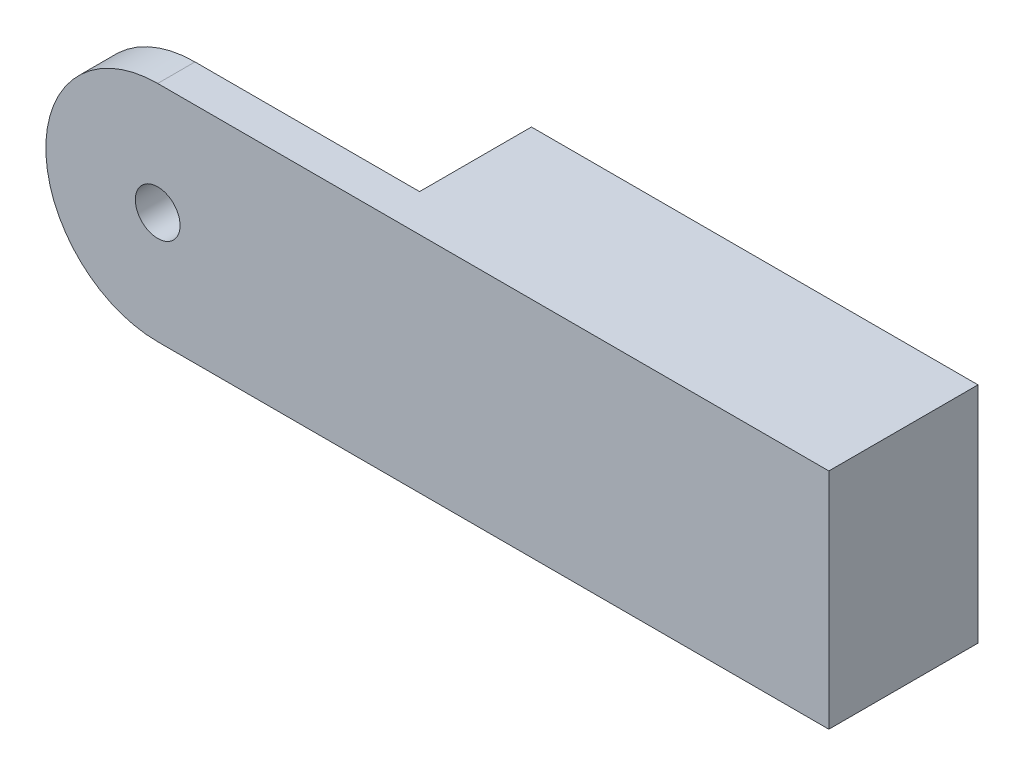
SolidWorks part; units mm, degrees
ref_plane "前视基准面" through (0, 0, 0) normal (0, 0, 1) x (1, 0, 0)
ref_plane "上视基准面" through (0, 0, 0) normal (0, 1, 0) x (1, 0, 0)
ref_plane "右视基准面" through (0, 0, 0) normal (1, 0, 0) x (0, 0, -1)
sketch "草图1" plane through (0, 0, 0) normal (0, 0, 1) x (1, 0, 0)
  line L1 (-45, 15) -> (45, 15)
  line L3 (-45, -15) -> (45, -15)
  line L4 (45, 15) -> (45, -15)
  arc A0 (-45, 15) -> (-45, -15) centre (-45, 0) ccw
  circle A1 centre (-45, 0) radius 3
  point P0 (0, 0)
  dimension "D1" = 30
extrude "凸台-拉伸1" add sketch "草图1" along normal blind 20
ref_plane "基准面1" through (0, 0, 15) normal (0, 0, 1) x (1, 0, 0)
sketch "草图2" plane through (0, 0, 15) normal (0, 0, 1) x (1, 0, 0)
  line L0 (45, 15) -> (-45, 15) construction
  line L1 (-29.6441, 15) -> (-61.6301, 15)
  line L2 (-29.6441, 15) -> (-29.6441, -15)
  line L3 (-29.6441, -15) -> (-61.6301, -15)
  line L4 (-61.6301, 15) -> (-61.6301, -15)
extrude "切除-拉伸2" cut sketch "草图2" against normal through all
sketch "草图3" plane through (0, 0, 15) normal (0, 0, 1) x (1, 0, 0)
  line L0 (45, 15) -> (-29.6441, 15) construction
  line L1 (-14.884, 15) -> (-59.884, 15)
  line L2 (-14.884, 15) -> (-14.884, -15)
  line L3 (-14.884, -15) -> (-59.884, -15)
  line L4 (-59.884, 15) -> (-59.884, -15)
  dimension "D1" = 45
extrude "切除-拉伸3" cut sketch "草图3" against normal through all
ref_axis "基准轴Hand" through (-45, 0, 20) along (0, 0, -1)
